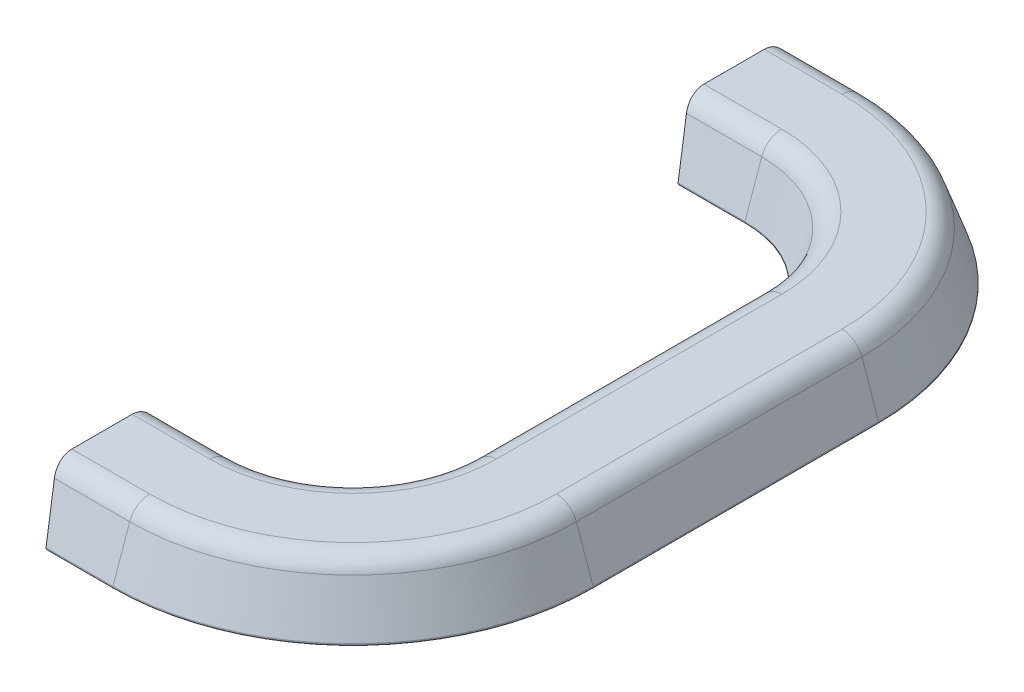
SolidWorks part; units mm, degrees
note: '?' marks a value the reader was unsure of.
material "Cast Alloy Steel"
ref_plane "Front Plane" through (0, 0, 0) normal (0, 0, 1) x (1, 0, 0)
ref_plane "Top Plane" through (0, 0, 0) normal (0, 1, 0) x (1, 0, 0)
ref_plane "Right Plane" through (0, 0, 0) normal (1, 0, 0) x (0, 0, -1)
sketch "Sketch1" plane through (0, 0, 0) normal (1, 0, 0) x (0, 0, -1)
  line L0 (-75.9772, 0) -> (-75.9772, 15.3502) construction
  line L1 (-92.2304, 0) -> (-59.724, 0)
  line L2 (-92.2304, 0) -> (-86.8199, 15.3502)
  line L3 (-86.8199, 15.3502) -> (-65.1345, 15.3502)
  line L4 (-59.724, 0) -> (-65.1345, 15.3502)
sketch "Sketch2" plane through (0, 0, 0) normal (0, 1, 0) x (1, 0, 0)
  line L0 (0, -59.724) -> (18.7014, -59.724)
  line L1 (44.1014, -34.324) -> (44.1014, 34.324)
  line L2 (18.7014, 59.724) -> (0, 59.724)
  line L3 (0, 0) -> (44.1014, 0) construction
  arc A0 (18.7014, -59.724) -> (44.1014, -34.324) centre (18.7014, -34.324) ccw
  arc A1 (44.1014, 34.324) -> (18.7014, 59.724) centre (18.7014, 34.324) ccw
  dimension "D1" = 25.4
sweep "Sweep1" add profiles "Sketch1" path "Sketch2"
ref_axis "Axis1" through (0, 0, 50) along (0, 0, -1)?
ref_plane "Plane1" through (2.625, 0.4629, 0) normal (-0.9848, -0.1736, 0) x (0, 0, 1)
other "SurfaceCut1"
fillet "Fillet1" radius 5.08 10 edges at (9.3507, 15.3502, -65.1345) (40.4877, 15.3502, -56.1103) (49.5119, 15.3502, 0) (40.4877, 15.3502, 56.1103) (9.3507, 15.3502, -86.8199) (55.8216, 15.3502, -71.4442) (71.1973, 15.3502, 0) (55.8216, 15.3502, 71.4442) (9.3507, 15.3502, 65.1345) (9.3507, 15.3502, 86.8199)
shell "Shell1" thickness 2.54
sketch "Sketch4" plane through (2.625, 0.4629, 0) normal (-0.9848, -0.1736, 0) x (0, 0, 1)
  line L1 (-75.9772, 15.117) -> (-75.9772, 8.7828) construction
  line L2 (-68.7303, 15.117) -> (-83.2241, 15.117) construction
  line L3 (-78.9482, 12.5378) -> (-78.5996, 8.5533)
  line L4 (-68.7303, 12.5378) -> (-83.2241, 12.5378) construction
  line L5 (-73.0062, 12.5378) -> (-73.3548, 8.5533)
  line L7 (-78.9482, 12.5378) -> (-73.0062, 12.5378)
  arc A0 (-78.5996, 8.5533) -> (-73.3548, 8.5533) centre (-75.9772, 8.7828) ccw
  dimension "D1" = 2.6324
  dimension "D2" = 8.9667
  dimension "D3" = 10
extrude "Extrude1" add sketch "Sketch4" against normal up to next
hole_wizard "7/64 (0.10938) Diameter Hole1" positions "Sketch6" profile "Sketch5" hole size "7/64" standard "Ansi Inch"
sketch "Sketch6" plane through (2.625, 0.4629, 0) normal (-0.9848, -0.1736, 0) x (0, 0, 1)
  point P0 (-75.9772, 8.7828)
sketch "Sketch5" plane through (1.0999, 9.1122, -75.9772) normal (0, 0, 1) x (0.1736, -0.9848, 0)
  line L0 (0, 0) -> (0, 13.5347)
  line L1 (0, 13.5347) -> (1.3891, 12.7)
  line L2 (1.3891, 12.7) -> (1.3891, 0)
  line L5 (1.3891, 0) -> (0, 0)
  line L10 (0, 13.5347) -> (-1.3891, 12.7) construction
  line L11 (0, -6.35) -> (0, 107.95) construction
  dimension "Hole Dia." = 2.7783
  dimension "Hole Depth" = 12.7
  dimension "Drill Angle" = 118
mirror "Mirror1" about plane through (0, 0, 0) normal (0, 0, 1) of "Extrude1", "7/64 (0.10938) Diameter Hole1"
fillet "Fillet2" radius 0.3969 16 edges at (36.6619, 0, 52.2845) (59.6474, 0, 75.27) (11.9208, 12.8102, -78.7739) (11.9208, 12.8102, -73.1805) (37.232, 12.8102, -75.9772) (11.9208, 12.8102, 78.7739) (37.232, 12.8102, 75.9772) (11.9208, 12.8102, 73.1805) (44.1014, 0, 0) (76.6078, 0, 0) (36.6619, 0, -52.2845) (59.6474, 0, -75.27) (10.704, 0, -59.724) (10.704, 0, -92.2304) (10.704, 0, 59.724) (10.704, 0, 92.2304)
